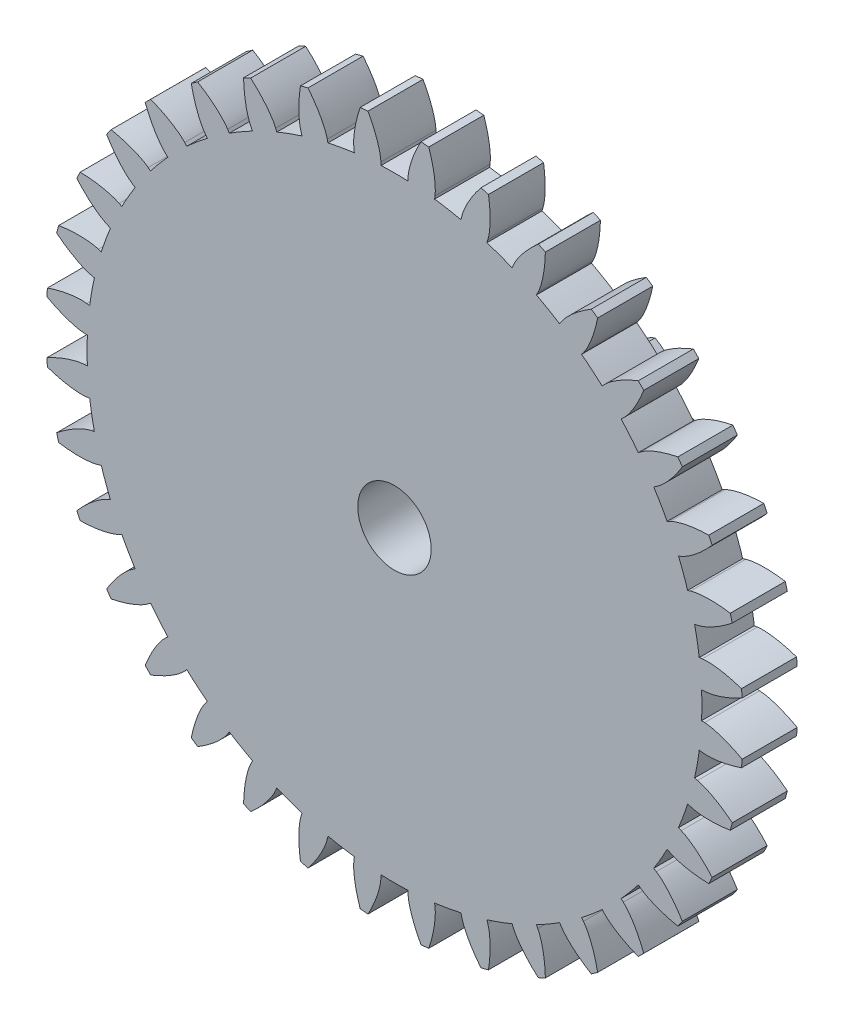
SolidWorks part; units mm, degrees
ref_plane "前视基准面" through (0, 0, 0) normal (0, 0, 1) x (1, 0, 0)
ref_plane "上视基准面" through (0, 0, 0) normal (0, 1, 0) x (1, 0, 0)
ref_plane "右视基准面" through (0, 0, 0) normal (1, 0, 0) x (0, 0, -1)
other "Configuration Table"
sketch "草图1" plane through (0, 0, 0) normal (0, 0, 1) x (1, 0, 0)
  line L0 (0, 0) -> (2.5, 0) construction
  line L1 (0, 0) -> (2.4692, 0.3911) construction
  line L2 (0, 0) -> (2.324, 0.3431)
  line L3 (2.4692, 0.3911) -> (2.4692, -0.3911) construction
  line L4 (0, 0) -> (2.324, -0.3431)
  circle A0 centre (0, 0) radius 3
  circle A1 centre (0, 0) radius 2.5 construction
  circle A2 centre (0, 0) radius 1.875
  circle A3 centre (0, 0) radius 2.3492 construction
  circle A4 centre (0, 0) radius 1
  spline S0 degree 4 poles (2.324, 0.3431) (2.3418, 0.3457) (2.3907, 0.3567) (2.48, 0.3921) (2.6156, 0.4687) (2.774, 0.5944) (2.9524, 0.7829) (3.1261, 1.0328) (3.2755, 1.3318) (3.3905, 1.6731) (3.4623, 2.0258) (3.4939, 2.3843) (3.4875, 2.7617) (3.431, 3.2258) (3.293, 3.7669) (3.0427, 4.3657) (2.6648, 4.9798) (2.2034, 5.533) (1.6708, 6.0186) (1.0824, 6.4323) (0.4456, 6.7712) (-0.2216, 7.0345) (-0.9214, 7.2211) (-1.5352, 7.3195) (-2.0864, 7.356) (-2.4818, 7.3587) (-2.8333, 7.3427) (-3.0656, 7.3237) (-3.3922, 7.2873) (-3.6372, 7.2455) (-3.8821, 7.2011) (-4.0043, 7.1711) (-4.0832, 7.1539) knots 0 0 0 0 0 0.005604 0.015718 0.02996 0.048734 0.068727 0.096889 0.125051 0.153212 0.181374 0.209535 0.237696 0.271429 0.327752 0.384075 0.440398 0.496721 0.553044 0.609367 0.66569 0.722013 0.778336 0.834659 0.86282 0.890982 0.909091 0.931818 0.954545 0.977273 1 1 1 1 1 construction
  spline S1 degree 4 poles (2.324, 0.3431) (2.3418, 0.3457) (2.3907, 0.3567) (2.48, 0.3921) (2.6156, 0.4687) (2.774, 0.5944) (2.9524, 0.7829) (3.1261, 1.0328) (3.2755, 1.3318) (3.3905, 1.6731) (3.4623, 2.0258) (3.4939, 2.3843) (3.4875, 2.7617) (3.431, 3.2258) (3.293, 3.7669) (3.0427, 4.3657) (2.6648, 4.9798) (2.2034, 5.533) (1.6708, 6.0186) (1.0824, 6.4323) (0.4456, 6.7712) (-0.2216, 7.0345) (-0.9214, 7.2211) (-1.5352, 7.3195) (-2.0864, 7.356) (-2.4818, 7.3587) (-2.7511, 7.3465) (-2.8848, 7.3375) (-2.9371, 7.3334) knots 0 0 0 0 0 0.005604 0.015718 0.02996 0.048734 0.068727 0.096889 0.125051 0.153212 0.181374 0.209535 0.237696 0.271429 0.327752 0.384075 0.440398 0.496721 0.553044 0.609367 0.66569 0.722013 0.778336 0.834659 0.86282 0.890982 0.909091 0.909091 0.909091 0.909091 0.909091
  spline S2 degree 4 poles (2.324, -0.3431) (2.3418, -0.3457) (2.3907, -0.3567) (2.48, -0.3921) (2.6156, -0.4687) (2.774, -0.5944) (2.9524, -0.7829) (3.1261, -1.0328) (3.2755, -1.3318) (3.3905, -1.6731) (3.4623, -2.0258) (3.4939, -2.3843) (3.4875, -2.7617) (3.431, -3.2258) (3.293, -3.7669) (3.0427, -4.3657) (2.6648, -4.9798) (2.2034, -5.533) (1.6708, -6.0186) (1.0824, -6.4323) (0.4456, -6.7712) (-0.2216, -7.0345) (-0.9214, -7.2211) (-1.5352, -7.3195) (-2.0864, -7.356) (-2.4818, -7.3587) (-2.8333, -7.3427) (-3.0656, -7.3237) (-3.3922, -7.2873) (-3.6372, -7.2455) (-3.8821, -7.2011) (-4.0043, -7.1711) (-4.0832, -7.1539) knots 0 0 0 0 0 0.005604 0.015718 0.02996 0.048734 0.068727 0.096889 0.125051 0.153212 0.181374 0.209535 0.237696 0.271429 0.327752 0.384075 0.440398 0.496721 0.553044 0.609367 0.66569 0.722013 0.778336 0.834659 0.86282 0.890982 0.909091 0.931818 0.954545 0.977273 1 1 1 1 1 construction
  spline S3 degree 4 poles (2.324, -0.3431) (2.3418, -0.3457) (2.3907, -0.3567) (2.48, -0.3921) (2.6156, -0.4687) (2.774, -0.5944) (2.9524, -0.7829) (3.1261, -1.0328) (3.2755, -1.3318) (3.3905, -1.6731) (3.4623, -2.0258) (3.4939, -2.3843) (3.4875, -2.7617) (3.431, -3.2258) (3.293, -3.7669) (3.0427, -4.3657) (2.6648, -4.9798) (2.2034, -5.533) (1.6708, -6.0186) (1.0824, -6.4323) (0.4456, -6.7712) (-0.2216, -7.0345) (-0.9214, -7.2211) (-1.5352, -7.3195) (-2.0864, -7.356) (-2.4818, -7.3587) (-2.7511, -7.3465) (-2.8848, -7.3375) (-2.9371, -7.3334) knots 0 0 0 0 0 0.005604 0.015718 0.02996 0.048734 0.068727 0.096889 0.125051 0.153212 0.181374 0.209535 0.237696 0.271429 0.327752 0.384075 0.440398 0.496721 0.553044 0.609367 0.66569 0.722013 0.778336 0.834659 0.86282 0.890982 0.909091 0.909091 0.909091 0.909091 0.909091
  point P15 (2.4692, 0)
  dimension "齿顶圆直径" = 6
  dimension "分度圆直径" = 5
  dimension "齿根圆直径" = 3.75
  dimension "基圆直径" = 4.6985
  dimension "内孔直径" = 2
  dimension "渐近线镜像线夹角" = 9
extrude "凸台-拉伸1" add sketch "草图1" along normal blind 4 contours A0 | A4
extrude "切除-拉伸1" cut sketch "草图1<3>" along normal through all contours A2 S3 A0 S1 region at (2.52, 0, 0)
sketch "草图1<3>" plane through (0, 0, 0) normal (0, 0, 1) x (1, 0, 0) same geometry as "草图1"
pattern_circular "阵列(圆周)1" count 10 every 36 about axis through (0, 0, 4) along (0, 0, 1) of "切除-拉伸1"
sketch "草图2" plane through (0, 0, 4) normal (0, 0, 1) x (1, 0, 0)
  line L0 (0, 0) -> (9, 0) construction
  line L1 (0, 0) -> (8.4492, 0.3689)
  line L2 (0, 0) -> (8.4492, -0.3689)
  line L3 (8.4492, 0.3689) -> (8.4492, -0.3689) construction
  circle A0 centre (0, 0) radius 9 construction
  circle A1 centre (0, 0) radius 8.4572 construction
  circle A2 centre (0, 0) radius 8.375
  circle A3 centre (0, 0) radius 9.5
  circle A4 centre (0, 0) radius 1
  spline S0 degree 4 poles (8.4492, -0.3689) (8.4814, -0.3703) (8.5454, -0.3761) (8.7233, -0.4082) (9.0528, -0.5094) (9.5332, -0.7316) (10.1397, -1.1329) (10.8371, -1.7552) (11.5364, -2.5985) (12.1635, -3.6256) (12.6799, -4.8148) (13.0452, -6.0581) (13.2678, -7.3342) (13.36, -8.6902) (13.2985, -10.3721) (12.9686, -12.355) (12.2527, -14.5792) (11.0854, -16.8971) (9.5976, -19.0222) (7.8373, -20.9263) (5.849, -22.5898) (3.946, -23.8233) (2.2222, -24.717) (0.735, -25.3515) (-0.4808, -25.7928) (-1.7188, -26.1677) (-2.9747, -26.4765) (-4.2454, -26.7194) (-5.3659, -26.8748) (-6.3322, -26.9675) (-7.0278, -27.0111) (-7.4576, -27.0297) (-7.8186, -27.0408) (-8.2008, -27.0477) (-8.5162, -27.0492) (-9.1168, -27.0434) (-9.5709, -27.026) (-10.133, -26.9992) (-10.6277, -26.9619) (-11.1643, -26.915) (-11.67, -26.8581) (-12.068, -26.8082) (-12.3203, -26.7716) (-12.4517, -26.7525) knots 0 0 0 0 0 0.002802 0.005604 0.015718 0.02996 0.048734 0.068727 0.096889 0.125051 0.153212 0.181374 0.209535 0.237696 0.271429 0.327752 0.384075 0.440398 0.496721 0.553044 0.609367 0.66569 0.693852 0.722013 0.750174 0.778336 0.806497 0.834659 0.86282 0.876901 0.890982 0.895509 0.900036 0.909091 0.920455 0.931818 0.943182 0.954545 0.965909 0.977273 0.988636 1 1 1 1 1 construction
  spline S1 degree 4 poles (8.4492, -0.3689) (8.4814, -0.3703) (8.5454, -0.3761) (8.7233, -0.4082) (9.0528, -0.5094) (9.5332, -0.7316) (10.1397, -1.1329) (10.8371, -1.7552) (11.5364, -2.5985) (12.1635, -3.6256) (12.6799, -4.8148) (13.0452, -6.0581) (13.2678, -7.3342) (13.36, -8.6902) (13.2985, -10.3721) (12.9686, -12.355) (12.2527, -14.5792) (11.0854, -16.8971) (9.5976, -19.0222) (7.8373, -20.9263) (5.849, -22.5898) (3.946, -23.8233) (2.2222, -24.717) (0.735, -25.3515) (-0.4808, -25.7928) (-1.7188, -26.1677) (-2.9747, -26.4765) (-4.2454, -26.7194) (-5.3659, -26.8748) (-6.3322, -26.9675) (-7.0278, -27.0111) (-7.4576, -27.0297) (-7.8186, -27.0408) (-8.0534, -27.045) (-8.1979, -27.0468) (-8.2923, -27.0474) knots 0 0 0 0 0 0.002802 0.005604 0.015718 0.02996 0.048734 0.068727 0.096889 0.125051 0.153212 0.181374 0.209535 0.237696 0.271429 0.327752 0.384075 0.440398 0.496721 0.553044 0.609367 0.66569 0.693852 0.722013 0.750174 0.778336 0.806497 0.834659 0.86282 0.876901 0.890982 0.895509 0.900036 0.909091 0.909091 0.909091 0.909091 0.909091
  spline S2 degree 4 poles (8.4492, 0.3689) (8.4814, 0.3703) (8.5454, 0.3761) (8.7233, 0.4082) (9.0528, 0.5094) (9.5332, 0.7316) (10.1397, 1.1329) (10.8371, 1.7552) (11.5364, 2.5985) (12.1635, 3.6256) (12.6799, 4.8148) (13.0452, 6.0581) (13.2678, 7.3342) (13.36, 8.6902) (13.2985, 10.3721) (12.9686, 12.355) (12.2527, 14.5792) (11.0854, 16.8971) (9.5976, 19.0222) (7.8373, 20.9263) (5.849, 22.5898) (3.946, 23.8233) (2.2222, 24.717) (0.735, 25.3515) (-0.4808, 25.7928) (-1.7188, 26.1677) (-2.9747, 26.4765) (-4.2454, 26.7194) (-5.3659, 26.8748) (-6.3322, 26.9675) (-7.0278, 27.0111) (-7.4576, 27.0297) (-7.8186, 27.0408) (-8.2008, 27.0477) (-8.5162, 27.0492) (-9.1168, 27.0434) (-9.5709, 27.026) (-10.133, 26.9992) (-10.6277, 26.9619) (-11.1643, 26.915) (-11.67, 26.8581) (-12.068, 26.8082) (-12.3203, 26.7716) (-12.4517, 26.7525) knots 0 0 0 0 0 0.002802 0.005604 0.015718 0.02996 0.048734 0.068727 0.096889 0.125051 0.153212 0.181374 0.209535 0.237696 0.271429 0.327752 0.384075 0.440398 0.496721 0.553044 0.609367 0.66569 0.693852 0.722013 0.750174 0.778336 0.806497 0.834659 0.86282 0.876901 0.890982 0.895509 0.900036 0.909091 0.920455 0.931818 0.943182 0.954545 0.965909 0.977273 0.988636 1 1 1 1 1 construction
  spline S3 degree 4 poles (8.4492, 0.3689) (8.4814, 0.3703) (8.5454, 0.3761) (8.7233, 0.4082) (9.0528, 0.5094) (9.5332, 0.7316) (10.1397, 1.1329) (10.8371, 1.7552) (11.5364, 2.5985) (12.1635, 3.6256) (12.6799, 4.8148) (13.0452, 6.0581) (13.2678, 7.3342) (13.36, 8.6902) (13.2985, 10.3721) (12.9686, 12.355) (12.2527, 14.5792) (11.0854, 16.8971) (9.5976, 19.0222) (7.8373, 20.9263) (5.849, 22.5898) (3.946, 23.8233) (2.2222, 24.717) (0.735, 25.3515) (-0.4808, 25.7928) (-1.7188, 26.1677) (-2.9747, 26.4765) (-4.2454, 26.7194) (-5.3659, 26.8748) (-6.3322, 26.9675) (-7.0278, 27.0111) (-7.4576, 27.0297) (-7.8186, 27.0408) (-8.0534, 27.045) (-8.1979, 27.0468) (-8.2923, 27.0474) knots 0 0 0 0 0 0.002802 0.005604 0.015718 0.02996 0.048734 0.068727 0.096889 0.125051 0.153212 0.181374 0.209535 0.237696 0.271429 0.327752 0.384075 0.440398 0.496721 0.553044 0.609367 0.66569 0.693852 0.722013 0.750174 0.778336 0.806497 0.834659 0.86282 0.876901 0.890982 0.895509 0.900036 0.909091 0.909091 0.909091 0.909091 0.909091
  point P16 (8.4492, 0)
  dimension "内孔直径" = 2
  dimension "分度圆直径" = 18
  dimension "齿顶圆直径" = 19
  dimension "基圆直径" = 16.9145
  dimension "齿根圆直径" = 16.75
  dimension "渐开线镜像线夹角" = 2.5
extrude "凸台-拉伸2" add sketch "草图2" along normal blind 1.5 contours A3 | A4
extrude "切除-拉伸3" cut sketch "草图2<3>" along normal through all contours S3 L1 A2 L2 S1 A3 region at (9.0018, 0, 4)
sketch "草图2<3>" plane through (0, 0, 4) normal (0, 0, 1) x (1, 0, 0) same geometry as "草图2"
pattern_circular "阵列(圆周)2" count 36 over 360 about axis through (0, 0, 5.5) along (0, 0, 1) of "切除-拉伸3"
equation "\"m\" = 0.5'模数"
equation "\"z\" = 10'齿数"
equation "\"a\"= 20度'压力角"
equation "\"d\"= \"m\" * \"z\"'分度圆直径"
equation "\"da\"= ( \"z\" + 2 ) * \"m\"'齿顶圆直径"
equation "\"df\"= ( \"z\" - 2.5 ) * \"m\"'齿根圆直径"
equation "\"s\"= 0.5 * PI * \"m\"'分度圆齿厚"
equation "\"r\"= 0.38 * \"m\"'齿根圆角"
equation "\"B\"= 0.3 * \"d\"'齿厚"
equation "\"db\"= \"m\" * \"z\" * cos ( \"a\" )'基圆直径"
equation "\"rb\"= \"db\" / 2'基圆半径"
equation "\"齿顶圆直径@草图1\"= \"da\""
equation "\"分度圆直径@草图1\"= \"d\""
equation "\"齿根圆直径@草图1\"= \"df\""
equation "\"基圆直径@草图1\"= \"db\""
equation "\"渐近线镜像线夹角@草图1\"= 360 / 4 / \"z\""
equation "\"h\" = 4'齿轮厚度"
equation "\"ir\"= 2'内孔直径"
equation "\"内孔直径@草图1\"= \"ir\""
equation "\"齿轮厚@凸台-拉伸1\"= \"h\""
equation "\"齿轮夹角@阵列(圆周)1\"= 360 / \"z\""
equation "\"齿数@阵列(圆周)1\"= \"z\""
equation "\"m1\" = 0.5'模数"
equation "\"z1\" = 36'齿数"
equation "\"a1\"= 20度'压力角"
equation "\"d1\"= \"m1\" * \"z1\"'分度圆直径"
equation "\"da1\"= ( \"z1\" + 2 ) * \"m1\"'齿顶圆直径"
equation "\"df1\"= ( \"z1\" - 2.5 ) * \"m1\"'齿根圆直径"
equation "\"s1\"= 0.5 * PI * \"m1\"'分度圆齿厚"
equation "\"r1\"= 0.38 * \"m1\"'齿根圆角"
equation "\"B1\"= 0.3 * \"d1\"'齿厚"
equation "\"db1\"= \"m1\" * \"z1\" * cos ( \"a1\" )'基圆直径"
equation "\"rb1\"= \"db1\" / 2'基圆半径"
equation "\"分度圆直径@草图2\"= \"d1\""
equation "\"齿顶圆直径@草图2\"= \"da1\""
equation "\"基圆直径@草图2\"= \"db1\""
equation "\"齿根圆直径@草图2\"= \"df1\""
equation "\"渐开线镜像线夹角@草图2\"= 360 / 4 / \"z1\""
equation "\"内孔直径@草图2\"= \"ir\""
equation "\"二层齿轮厚@凸台-拉伸2\" = \"h1\""
equation "\"h1\" = 1.5'齿轮厚度"
equation "\"二层齿数@阵列(圆周)2\"= \"z1\""
